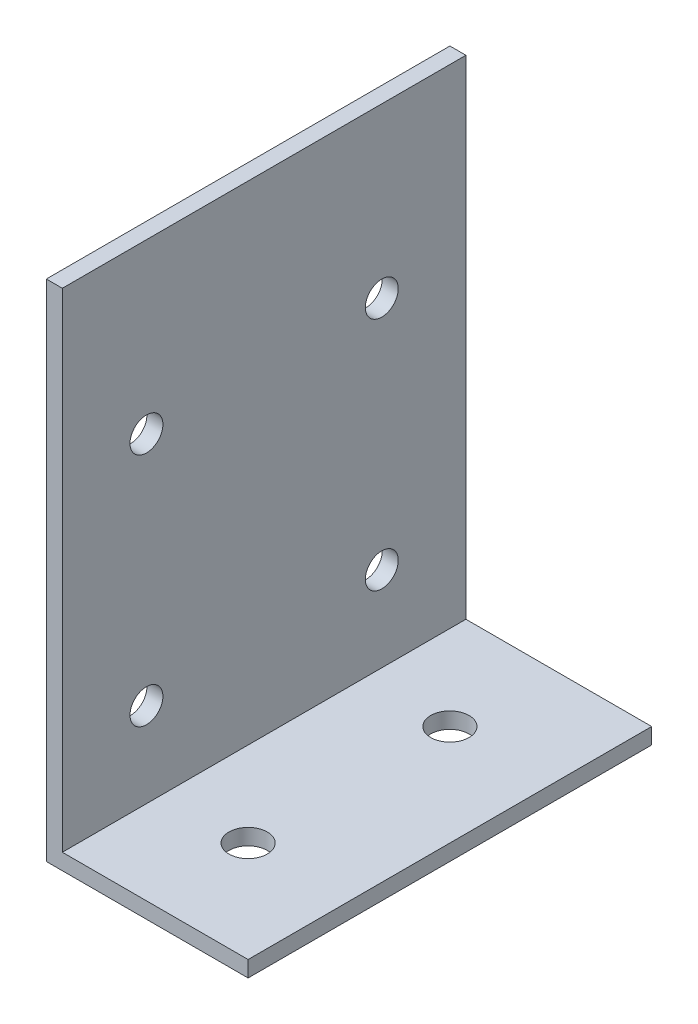
SolidWorks part; units mm, degrees
ref_plane "Front Plane" through (0, 0, 0) normal (0, 0, 1) x (1, 0, 0)
ref_plane "Top Plane" through (0, 0, 0) normal (0, 1, 0) x (1, 0, 0)
ref_plane "Right Plane" through (0, 0, 0) normal (1, 0, 0) x (0, 0, -1)
sketch "Sketch1" plane through (0, 0, 0) normal (0, 0, 1) x (1, 0, 0)
  line L0 (0, 50) -> (0, 0)
  line L1 (0, 0) -> (20, 0)
  line L2 (1.5875, 50) -> (1.5875, 1.5875)
  line L3 (1.5875, 1.5875) -> (20, 1.5875)
  line L4 (0, 50) -> (1.5875, 50)
  line L5 (20, 1.5875) -> (20, 0)
  dimension "D1" = 50
  dimension "D2" = 20
  dimension "D3" = 1.5875
extrude "Boss-Extrude1" add sketch "Sketch1" along normal blind 20
hole_wizard "#4 Clearance Hole1" positions "Sketch3" profile "Sketch2" hole size "#4" standard "ANSI Inch" end condition through all
sketch "Sketch3" plane through (0, 0, 0) normal (-1, 0, 0) x (0, 0, 1)
  line L0 (0, 50) -> (0, 0) construction
  line L1 (20, 0) -> (0, 0) construction
  point P0 (11.6625, 33.325)
  point P2 (11.6625, 10)
  dimension "D1" = 11.6625
  dimension "D2" = 23.325
  dimension "D3" = 10
sketch "Sketch2" plane through (0, 33.325, 11.6625) normal (0, 1, 0) x (0, 0, 1)
  line L0 (0, 0) -> (0, 20)
  line L1 (0, 20) -> (1.6319, 20)
  line L2 (1.6319, 20) -> (1.6319, 0)
  line L5 (1.6319, 0) -> (0, 0)
  line L11 (0, -6.35) -> (0, 107.95) construction
  dimension "Thru Hole Dia." = 3.2639
  dimension "Thru Hole Depth" = 20
hole_wizard "#6 Clearance Hole1" positions "3DSketch1" profile "Sketch4" hole size "#6" standard "ANSI Inch" end condition through all
sketch3d "3DSketch1"
  line L0 (0, 0, 0) -> (20, 0, 0) construction
  line L1 (20, 0, 20) -> (20, 0, 0) construction
  point P0 (10, 0, 10)
  dimension "D1" = 10
  dimension "D2" = 10
sketch "Sketch4" plane through (10, 0, 10) normal (1, 0, 0) x (0, 0, -1)
  line L0 (0, 0) -> (0, 50)
  line L1 (0, 50) -> (1.8986, 50)
  line L2 (1.8986, 50) -> (1.8986, 0)
  line L5 (1.8986, 0) -> (0, 0)
  line L11 (0, -6.35) -> (0, 107.95) construction
  dimension "Thru Hole Dia." = 3.7973
  dimension "Thru Hole Depth" = 50
mirror "Mirror1" about plane through (0, 0, 0) normal (0, 0, -1) of "#6 Clearance Hole1", "#4 Clearance Hole1", "Boss-Extrude1"
